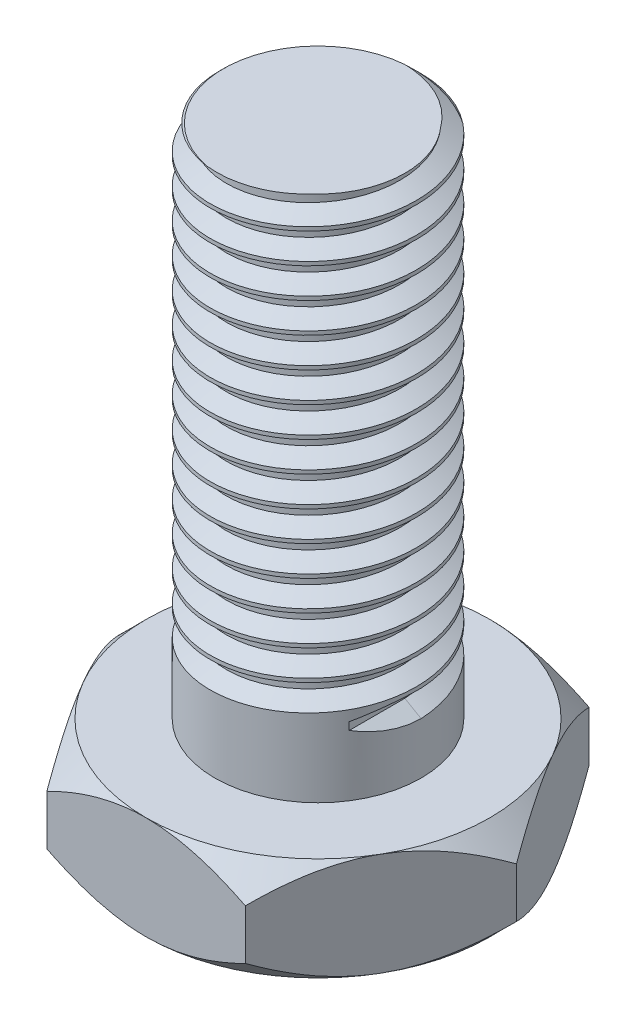
SolidWorks part; units mm, degrees
ref_plane "Front Plane" through (0, 0, 0) normal (0, 0, 1) x (1, 0, 0)
ref_plane "Top Plane" through (0, 0, 0) normal (0, 1, 0) x (1, 0, 0)
ref_plane "Right Plane" through (0, 0, 0) normal (1, 0, 0) x (0, 0, -1)
sketch "Sketch1" plane through (0, 0, 0) normal (0, 1, 0) x (1, 0, 0)
  line L1 (11.547, 0) -> (5.7735, 10)
  line L2 (5.7735, 10) -> (-5.7735, 10)
  line L3 (-5.7735, 10) -> (-11.547, 0)
  line L4 (-11.547, 0) -> (-5.7735, -10)
  line L5 (-5.7735, -10) -> (5.7735, -10)
  line L6 (5.7735, -10) -> (11.547, 0)
  circle A0 centre (0, 0) radius 10 construction
  dimension "D1" = 20
extrude "Boss-Extrude2" add sketch "Sketch1" along normal mid plane 6
sketch "Sketch3" plane through (0, 3, 0) normal (0, 1, 0) x (1, 0, 0)
  line L0 (5.7735, 10) -> (-5.7735, 10) construction
  circle A0 centre (0, 0) radius 10
extrude "Cut-Extrude5" cut sketch "Sketch3" against normal through all draft 45 flip side to cut
mirror "Mirror1" about plane through (0, 0, 0) normal (0, 1, 0) of "Cut-Extrude5"
sketch "Sketch4" plane through (0, 3, 0) normal (0, 1, 0) x (1, 0, 0)
  circle A0 centre (0, 0) radius 6
  dimension "D1" = 12
extrude "Boss-Extrude3" add sketch "Sketch4" along normal blind 30
chamfer "Chamfer2" distance 0.5 angle 45 1 edges at (0, 33, 6)
thread "Thread4" pitch 1.75 method cut profile "Thread Profile4" start angle 0, offset 3, length 0, pitch 1.75, diameter 12
ref_plane "Plane4" through (6, 6, 0) normal (0, 0, 1) x (1, 0, 0)
sketch "Thread Profile4" plane through (6, 6, 0) normal (0, 0, 1) x (1, 0, 0)
  line L0 (0, 0) -> (0, 1.75) construction
  line L11 (0, 0) -> (0, 1.5312)
  line L12 (0, 1.5312) -> (-0.9472, 0.9844)
  line L13 (-0.9472, 0.9844) -> (-0.9472, 0.5469)
  line L15 (-0.9472, 0.5469) -> (0, 0)
  line L17 (-0.9472, 0.7656) -> (0, 0.7656) construction
  point P2 (0, 0)
  dimension "Pitch" = 1.75
  dimension "Profile_Angle" = 60
  dimension "Profile_Land" = 0.4375
  dimension "Profile_Height" = 0.9472
sketch "Sketch15" plane through (0, 0, 0) normal (0, 0, -1) x (-1, 0, 0)
  line L4 (-6, 6) -> (-5.0528, 6.5469)
  line L5 (-5.0528, 6.5469) -> (-5.0528, 6.9844)
  line L6 (-5.0528, 6.9844) -> (-6, 7.5312)
  line L7 (-6, 7.5312) -> (-6, 6)
  line L8 (-6, 6) -> (-5.0528, 6.5469)
  line L9 (-5.0528, 6.5469) -> (-5.0528, 6.9844)
  line L10 (-5.0528, 6.9844) -> (-6, 7.5312)
  line L11 (-6, 7.5312) -> (-6, 6)
  dimension "D1" = 0
extrude "Cut-Extrude6" cut sketch "Sketch15" against normal blind 30 contours L8 L9 L10 L11
